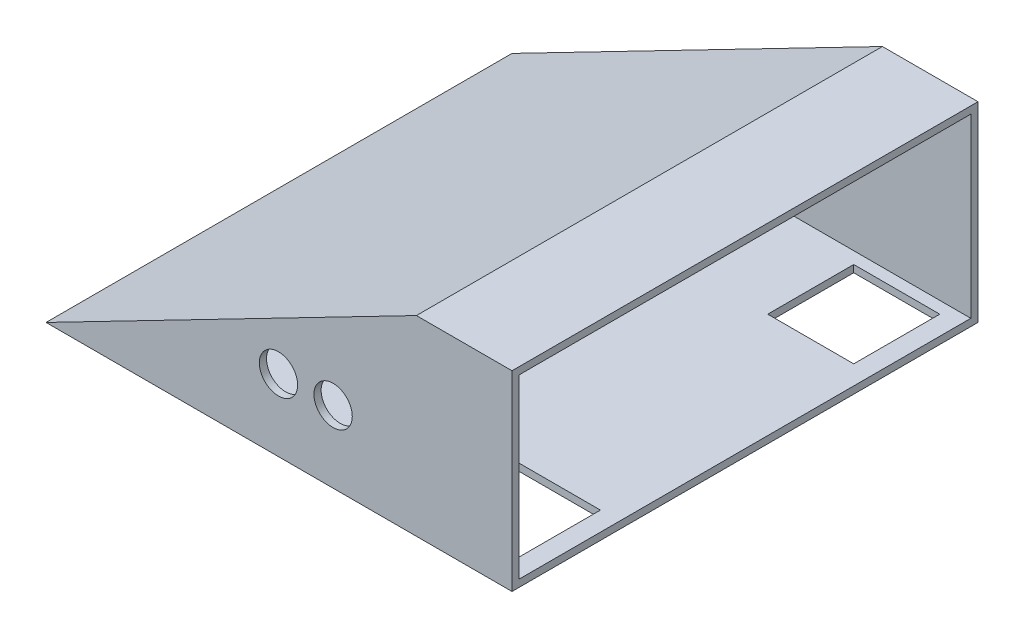
SolidWorks part; units mm, degrees
ref_plane "Front Plane" through (0, 0, 0) normal (0, 0, 1) x (1, 0, 0)
ref_plane "Top Plane" through (0, 0, 0) normal (0, 1, 0) x (1, 0, 0)
ref_plane "Right Plane" through (0, 0, 0) normal (1, 0, 0) x (0, 0, -1)
ref_plane "Plane1" through (0, 0, 0) normal (1, 0, 0) x (0, 0, -1)
ref_plane "Plane2" through (0, 0, 97.5) normal (0, 0, 1) x (1, 0, 0)
sketch "Sketch2" plane through (0, 0, 0) normal (0, 0, 1) x (1, 0, 0)
  line L0 (0, 0) -> (195, 0)
  line L1 (195, 0) -> (195, 80)
  line L2 (195, 80) -> (155, 80)
  line L3 (155, 80) -> (0, 0)
  dimension "D1" = 195
  dimension "D2" = 40
  dimension "80" = 80
extrude "Robot" add sketch "Sketch2" along normal blind 195
sketch "Sketch3" plane through (0, 0, 195) normal (0, 0, 1) x (1, 0, 0)
  line L0 (0, 0) -> (195, 0) construction
  line L2 (155, 80) -> (0, 0) construction
  circle A0 centre (97.2899, 30) radius 8.02
  circle A1 centre (120.1399, 30) radius 8.02
  dimension "D1" = 30
  dimension "D2" = 16.04
  dimension "D4" = 16.04
  dimension "D3" = 22.85
  dimension "D5" = 30
  dimension "D6" = 17.9627
sketch "Arriba" plane through (0, 80, 0) normal (0, 1, 0) x (1, 0, 0)
  line L0 (195, 0) -> (195, -195) construction
  line L1 (0, 0) -> (0, -195) construction
  line L2 (0, -97.5) -> (195, -97.5) construction
  line L3 (0, 0) -> (195, 0) construction
  line L4 (0, -195) -> (195, -195) construction
  line L5 (97.5, 0) -> (97.5, -195) construction
sketch "Adelante" plane through (0, 0, 0) normal (1, 0, 0) x (0, 0, -1)
  line L0 (0, 80) -> (0, 0) construction
  line L1 (-97.5, 80) -> (-97.5, 0) construction
  line L2 (0, 80) -> (-195, 80) construction
  line L3 (-195, 0) -> (0, 0) construction
  line L4 (-195, 80) -> (-195, 0) construction
  line L5 (0, 0) -> (-195, 0) construction
  point P14 (0, 0)
sketch "Sketch9" plane through (0, 0, 0) normal (0, 0, -1) x (-1, 0, 0)
  line L0 (-155, 80) -> (0, 0) construction
  line L1 (0, 0) -> (-195, 0) construction
  circle A0 centre (-97.284, 30) radius 8.2
  circle A1 centre (-120.134, 30) radius 8.2
  dimension "D1" = 17.96
  dimension "D2" = 16.4
  dimension "D4" = 30
  dimension "D6" = 16.4
  dimension "D3" = 30
  dimension "D5" = 22.85
sketch "Sketch10" plane through (0, 0, 0) normal (0, -1, 0) x (-1, 0, 0)
  line L0 (0, -195) -> (-195, -195) construction
  line L1 (-187, -187) -> (-150, -187)
  line L2 (-187, -187) -> (-187, -150)
  line L3 (-187, -150) -> (-150, -150)
  line L4 (-150, -187) -> (-150, -150)
  line L5 (-195, 0) -> (-195, -195) construction
  dimension "D1" = 8
  dimension "D2" = 8
  dimension "D3" = 37
  dimension "D4" = 37
sketch "Sketch12" plane through (0, 0, 0) normal (0, -1, 0) x (-1, 0, 0)
  line L0 (-195, 0) -> (-195, -195) construction
  line L1 (-187, -44) -> (-151, -44)
  line L2 (-187, -44) -> (-187, -8)
  line L3 (-187, -8) -> (-151, -8)
  line L4 (-151, -44) -> (-151, -8)
  line L5 (0, 0) -> (-195, 0) construction
  dimension "D1" = 8
  dimension "D2" = 8
  dimension "D3" = 36
  dimension "D4" = 36
sketch "Sketch13" plane through (0, 0, 0) normal (0, -1, 0) x (1, 0, 0)
  line L0 (0, 0) -> (195, 0) construction
  line L1 (15, 8) -> (22.4, 8)
  line L2 (15, 8) -> (15, 15.4)
  line L3 (15, 15.4) -> (22.4, 15.4)
  line L4 (22.4, 8) -> (22.4, 15.4)
  line L5 (0, 0) -> (0, 195) construction
  dimension "D1" = 8
  dimension "D2" = 15
  dimension "D3" = 7.4
  dimension "D4" = 7.4
sketch "Sketch14" plane through (0, 0, 0) normal (0, -1, 0) x (-1, 0, 0)
  line L0 (0, -195) -> (-195, -195) construction
  line L1 (-15, -179.6) -> (-22.4, -179.6)
  line L2 (-15, -179.6) -> (-15, -187)
  line L3 (-15, -187) -> (-22.4, -187)
  line L4 (-22.4, -179.6) -> (-22.4, -187)
  line L5 (0, 0) -> (0, -195) construction
  dimension "D1" = 8
  dimension "D2" = 15
  dimension "D3" = 7.4
  dimension "D4" = 7.4
sketch "Sketch15" plane through (0, 0, 0) normal (0, -1, 0) x (-1, 0, 0)
  line L0 (0, -97.5) -> (-195, -97.5) construction
  line L1 (-15, -93.98) -> (-22.04, -93.98)
  line L2 (-15, -93.98) -> (-15, -101.02)
  line L3 (-15, -101.02) -> (-22.04, -101.02)
  line L4 (-22.04, -93.98) -> (-22.04, -101.02)
  line L5 (0, 0) -> (0, -195) construction
  dimension "D1" = 3.52
  dimension "D2" = 3.52
  dimension "D3" = 7.04
  dimension "D4" = 15
shell "Vacio por dentro 3mm" thickness 3 removed face at (195, 40, 97.5)
extrude "Ultrasonico Derecha" cut sketch "Sketch3" against normal blind 3
extrude "Ultrasonico Izquierda" cut sketch "Sketch9" against normal blind 3
extrude "Rueda Derecha" cut sketch "Sketch10" against normal blind 3
extrude "Rueda Izquierda" cut sketch "Sketch12" against normal blind 3
extrude "Cyn70 Derecha" cut sketch "Sketch14" against normal blind 4
extrude "Cny70 Centro" cut sketch "Sketch15" against normal blind 4
extrude "Cny70 Izquierda" cut sketch "Sketch13" against normal blind 4
